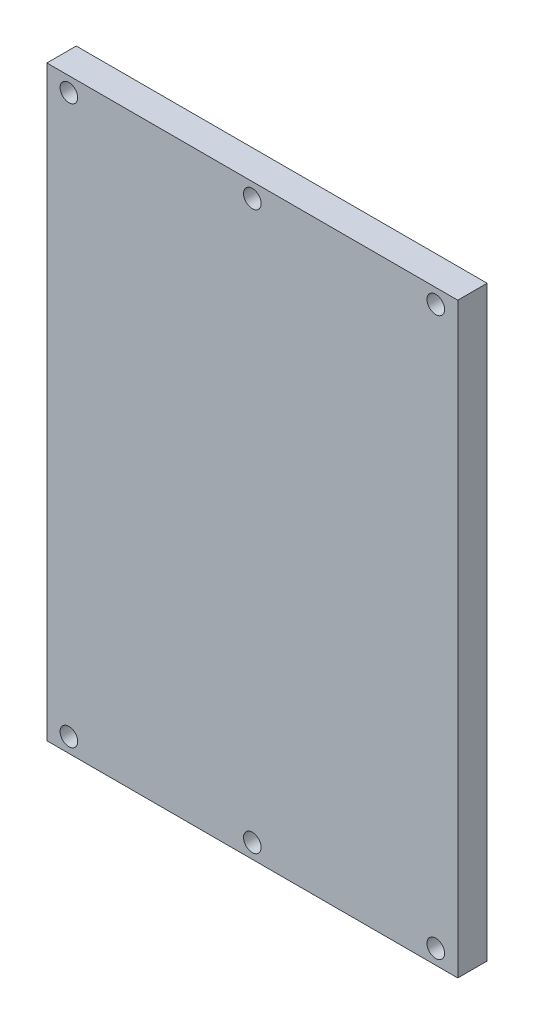
SolidWorks part; units mm, degrees
ref_plane "Front Plane" through (0, 0, 0) normal (0, 0, 1) x (1, 0, 0)
ref_plane "Top Plane" through (0, 0, 0) normal (0, 1, 0) x (1, 0, 0)
ref_plane "Right Plane" through (0, 0, 0) normal (1, 0, 0) x (0, 0, -1)
sketch "Sketch1" plane through (0, 0, 0) normal (0, 0, 1) x (1, 0, 0)
  line L1 (-35, -50) -> (35, -50)
  line L2 (-35, -50) -> (-35, 50)
  line L3 (-35, 50) -> (35, 50)
  line L4 (35, -50) -> (35, 50)
  line L5 (-35, -50) -> (35, 50) construction
  line L6 (-35, 50) -> (35, -50) construction
  point P0 (0, 0)
  dimension "D1" = 70
  dimension "D2" = 100
extrude "Boss-Extrude1" add sketch "Sketch1" along normal mid plane 5
sketch "Sketch2" plane through (0, 0, 2.5) normal (0, 0, 1) x (1, 0, 0)
  line L0 (0, 0) -> (0, 47.5)
  line L1 (0, 47.5) -> (-31.25, 47.5)
  circle A0 centre (0, 47.5) radius 1.5
  circle A1 centre (-31.25, 47.5) radius 1.5
  circle A2 centre (31.25, 47.5) radius 1.5
  dimension "D2" = 3
  dimension "D4" = 3
  dimension "D1" = 47.5
  dimension "D3" = 31.25
extrude "Cut-Extrude1" cut sketch "Sketch2" against normal blind 11 contours A2 | A1 | A0
mirror "Mirror1" about plane through (0, 0, 0) normal (0, 1, 0) of "Cut-Extrude1"
sketch "Sketch3" plane through (0, 0, 2.5) normal (0, 0, 1) x (1, 0, 0)
  line L0 (-35, 50) -> (-35, 15)
  line L1 (-35, 50) -> (-35, -50) construction
  line L2 (-35, 15) -> (35, 15)
  line L3 (35, -50) -> (35, 50) construction
  line L4 (-35, 15) -> (-35, -20)
  line L5 (-35, -20) -> (35, -20)
  line L6 (-35, 32.5) -> (35, 32.5)
  line L7 (-35, -2.5) -> (0, -2.5)
  line L8 (0, -20) -> (0, -50)
  line L9 (-35, -50) -> (35, -50) construction
  line L11 (-25, -49) -> (25, -49)
  line L12 (-25, -49) -> (-25, -21)
  line L13 (-25, -21) -> (25, -21)
  line L14 (25, -49) -> (25, -21)
  line L15 (-25, -49) -> (25, -21) construction
  line L16 (-25, -21) -> (25, -49) construction
  circle A0 centre (0, 32.5) radius 1.5
  circle A1 centre (7, 32.5) radius 1.5
  circle A2 centre (0, 32.5) radius 1.5
  circle A3 centre (-7, 32.5) radius 1.5
  circle A4 centre (0, -2.5) radius 1.5
  circle A5 centre (7, -2.5) radius 1.5
  circle A6 centre (0, -2.5) radius 1.5
  circle A7 centre (-7, -2.5) radius 1.5
  point P33 (0, -35)
  dimension "D3" = 3
  dimension "D6" = 3
  dimension "D1" = 35
  dimension "D2" = 35
  dimension "D9" = 28
  dimension "D10" = 50
  dimension "D4" = 2
  dimension "D5" = 2
  dimension "D7" = 2
  dimension "D8" = 2
